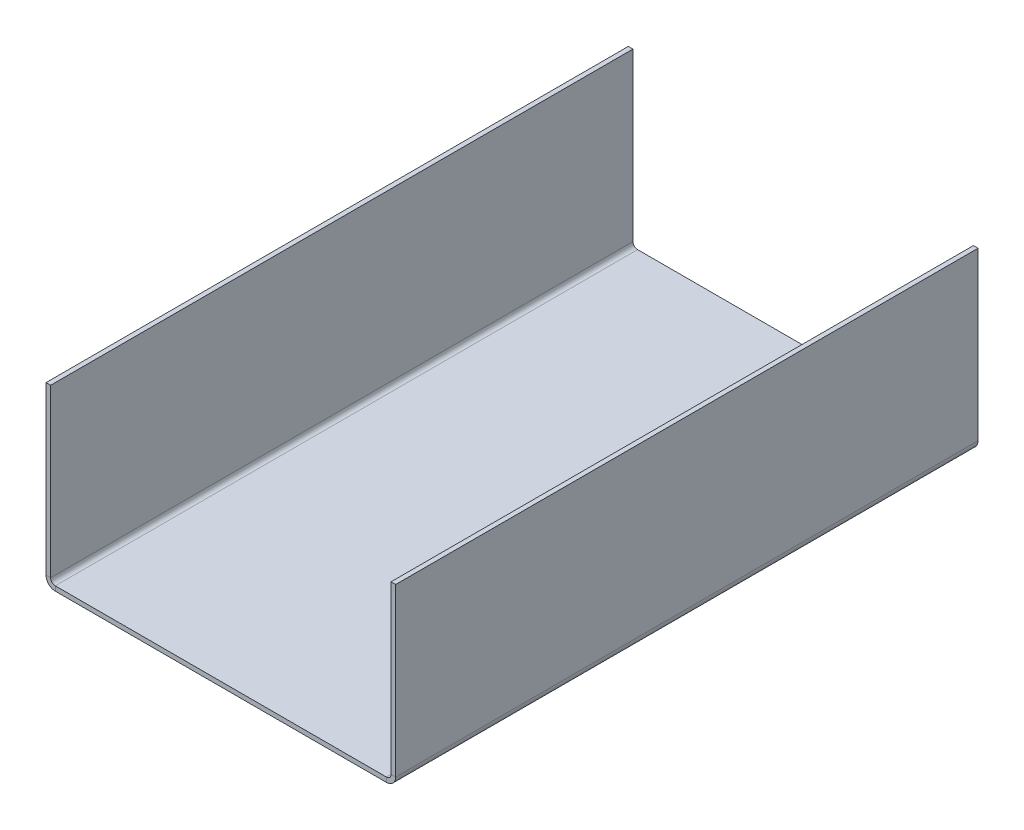
SolidWorks part; units mm, degrees
note: The reader was unsure of these and kept them because the rebuilt part matched: flange length of "Ребро-кромка1".
ref_plane "Спереди" through (0, 0, 0) normal (0, 0, 1) x (1, 0, 0)
ref_plane "Сверху" through (0, 0, 0) normal (0, 1, 0) x (1, 0, 0)
ref_plane "Справа" through (0, 0, 0) normal (1, 0, 0) x (0, 0, -1)
sketch "Эскиз2" plane through (0, 0, 0) normal (0, 1, 0) x (1, 0, 0)
  line L1 (-36.7468, -62.8655) -> (36.7468, -62.8655)
  line L2 (-36.7468, -62.8655) -> (-36.7468, 62.8655)
  line L3 (-36.7468, 62.8655) -> (36.7468, 62.8655)
  line L4 (36.7468, -62.8655) -> (36.7468, 62.8655)
  line L5 (-36.7468, -62.8655) -> (36.7468, 62.8655) construction
  line L6 (-36.7468, 62.8655) -> (36.7468, -62.8655) construction
  point P0 (0, 0)
base flange "Базовая кромка1" sketch "Эскиз2" thickness 1 reverse thickness direction no parameters "D1"=1
edge flange "Ребро-кромка1" sketch "Эскиз9" flange angle 90 flange length 38 flange position material outside bend radius 1 thickness 1 relief rectangular parameters "D6"=10
sketch "Эскиз9" plane through (36.7468, 0, 0) normal (1, 0, 0) x (0, 0, -1)
  line L0 (-62.8655, 0) -> (62.8655, 0) construction
  line L1 (-62.8655, 0) -> (62.8655, 0)
  line L2 (-62.8655, 0) -> (-62.8655, 37)
  line L3 (-62.8655, 37) -> (62.8655, 37)
  line L4 (62.8655, 37) -> (62.8655, 0)
bend "EdgeBend1" bend radius 1 bend angle 90 parameters "D5"=1
mirror "Зеркальное отражение1" about plane through (0, 0, 0) normal (1, 0, 0) of "Ребро-кромка1"
bend "Зеркальное отражение сгиба1" bend radius 1 bend angle 90 parameters "D5"=2
sketch "Сгиб-Линии1" [suppressed] plane through (0, 0, 0) normal (0, 1, 0) x (1, 0, 0)
sketch "Граничная рамка1" [suppressed] plane through (0, 0, 0) normal (0, 1, 0) x (1, 0, 0)
sheet metal parameters "Листовой металл1" thickness 1 parameters "D1"=1
flat pattern "Развертка1" [suppressed]
sketch "Сгиб-Линии2" plane through (0, 0, 0) normal (0, 1, 0) x (1, 0, 0)
sketch3d "Граничная рамка2" [suppressed]
  line L0 (36.7468, -62.8655, 0) -> (36.7468, 62.8655, 0) construction
  line L1 (-36.7468, -62.8655, 0) -> (-36.7468, 62.8655, 0) construction
  line L2 (36.7468, -62.8655, 0) -> (-36.7468, -62.8655, 0) construction
  line L3 (36.7468, 62.8655, 0) -> (-36.7468, 62.8655, 0) construction
sheet metal parameters "Листовой металл2" thickness 1 parameters "D1"=1
flat pattern "Развертка1"
sketch "Сгиб-Линии2" plane through (0, 0, 0) normal (0, 1, 0) x (1, 0, 0)
  line L0 (36.9249, -62.8655) -> (36.9249, 62.8655) construction
  line L1 (36.9249, -62.8655) -> (36.9249, 62.8655) construction
sketch3d "Граничная рамка2" [suppressed]
  line L0 (-36.7468, -62.8655, 0) -> (-36.7468, 62.8655, 0) construction
  line L1 (74.103, -62.8655, 0) -> (74.103, 62.8655, 0) construction
  line L2 (-36.7468, -62.8655, 0) -> (74.103, -62.8655, 0) construction
  line L3 (-36.7468, 62.8655, 0) -> (74.103, 62.8655, 0) construction
bend of the flat pattern "Плоское состояние-<EdgeBend1>1"
sheet metal parameters "Листовой металл3" thickness 1 parameters "D1"=1
flat pattern "Развертка1"
sketch "Сгиб-Линии2" plane through (0, 0, 0) normal (0, 1, 0) x (1, 0, 0)
  line L0 (36.9249, -62.8655) -> (36.9249, 62.8655) construction
  line L1 (36.9249, -62.8655) -> (36.9249, 62.8655) construction
  line L2 (-36.9249, 62.8655) -> (-36.9249, -62.8655) construction
  line L3 (-36.9249, 62.8655) -> (-36.9249, -62.8655) construction
sketch3d "Граничная рамка2" [suppressed]
  line L0 (74.103, 62.8655, 0) -> (-74.103, 62.8655, 0) construction
  line L1 (74.103, -62.8655, 0) -> (-74.103, -62.8655, 0) construction
  line L2 (74.103, 62.8655, 0) -> (74.103, -62.8655, 0) construction
  line L3 (-74.103, 62.8655, 0) -> (-74.103, -62.8655, 0) construction
bend of the flat pattern "Плоское состояние-<EdgeBend1>1"
bend of the flat pattern "Плоское состояние-<Зеркальное отражение сгиба1>1"
